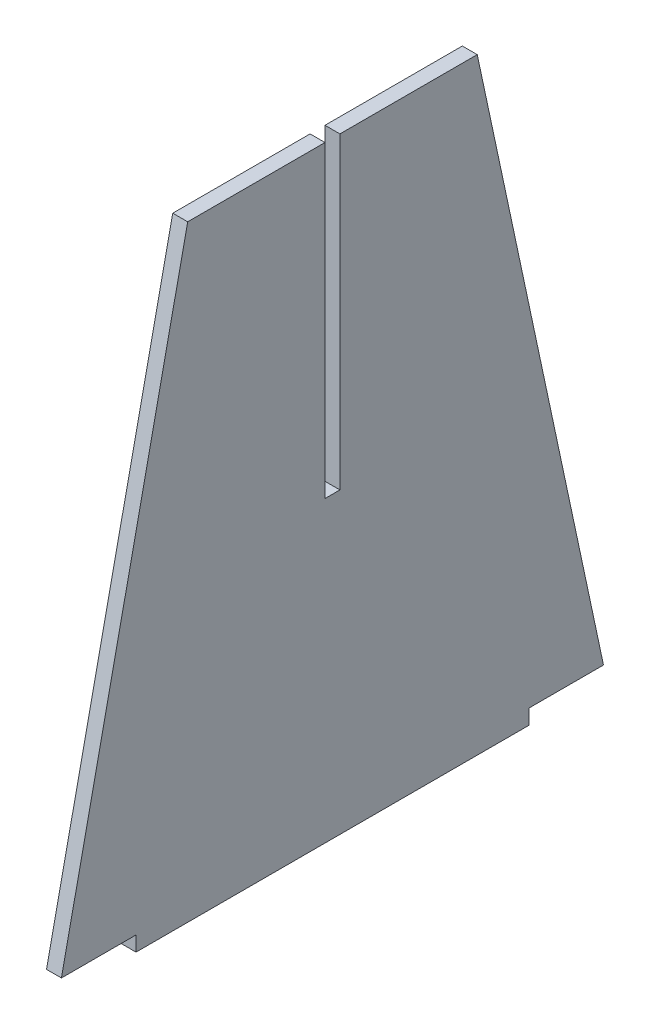
SolidWorks part; units mm, degrees
ref_plane "Спереди" through (0, 0, 0) normal (0, 0, 1) x (1, 0, 0)
ref_plane "Сверху" through (0, 0, 0) normal (0, 1, 0) x (1, 0, 0)
ref_plane "Справа" through (0, 0, 0) normal (1, 0, 0) x (0, 0, -1)
sketch "Эскиз1" plane through (0, 0, 0) normal (1, 0, 0) x (0, 0, -1)
  line L3 (29.1133, 119) -> (54.5, 0)
  line L4 (54.5, 0) -> (39.5, 0)
  line L5 (39.5, 0) -> (39.5, -3)
  line L6 (39.5, -3) -> (-39.5, -3)
  line L9 (1.5, 57) -> (1.5, 119)
  line L10 (0, -3) -> (0, 75) construction
  line L11 (-1.5, 57) -> (-1.5, 119)
  line L12 (-39.5, 0) -> (-39.5, -3)
  line L13 (-54.5, 0) -> (-39.5, 0)
  line L14 (-29.1133, 119) -> (-54.5, 0)
  line L16 (-1.5, 119) -> (-29.1133, 119)
  line L17 (29.1133, 119) -> (1.5, 119)
  line L20 (1.5, 57) -> (-1.5, 57)
extrude "Бобышка-Вытянуть1" add sketch "Эскиз1" along normal blind 3
